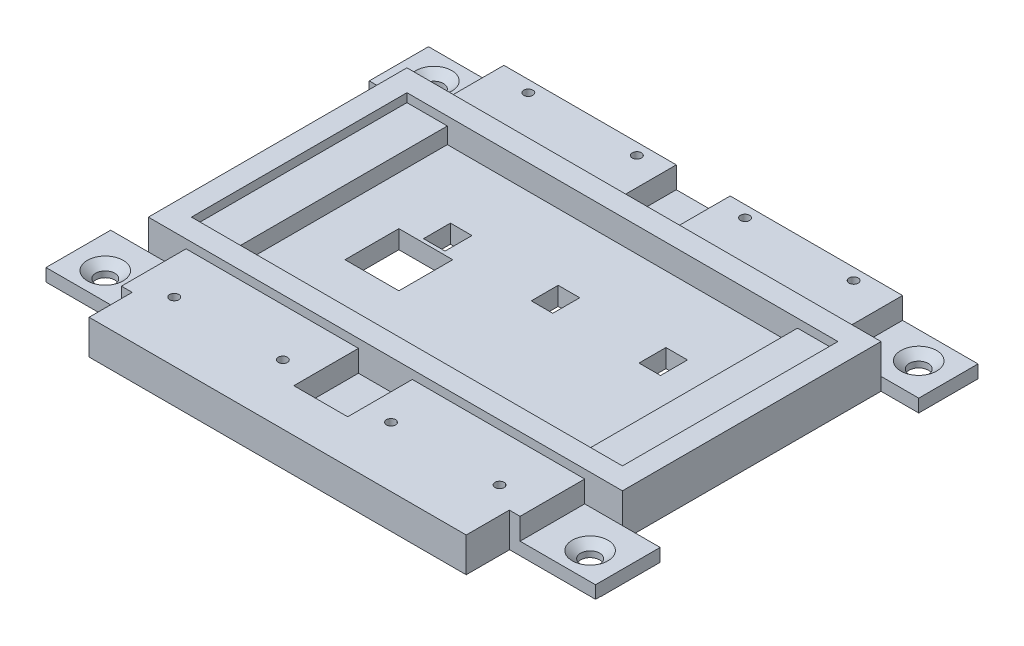
SolidWorks part; units mm, degrees
ref_plane "Front Plane" through (0, 0, 0) normal (0, 0, 1) x (1, 0, 0)
ref_plane "Top Plane" through (0, 0, 0) normal (0, 1, 0) x (1, 0, 0)
ref_plane "Right Plane" through (0, 0, 0) normal (1, 0, 0) x (0, 0, -1)
sketch "Sketch5" plane through (0, 5.08, 0) normal (0, 1, 0) x (1, 0, 0)
  line L0 (5.08, 5.08) -> (5.08, 248.92) construction
  line L1 (5.08, 105.41) -> (134.62, 105.41)
  line L2 (5.08, 105.41) -> (5.08, 16.51)
  line L3 (5.08, 16.51) -> (134.62, 16.51)
  line L4 (134.62, 105.41) -> (134.62, 16.51)
  line L6 (134.62, 248.92) -> (134.62, 5.08) construction
  point P8 (134.62, 60.96)
  dimension "D1" = 60.96
  dimension "D2" = 88.9
extrude "Button Support" add sketch "Sketch5" along normal blind 48.768
ref_plane "Plane1" through (0, 0, -60.96) normal (0, 0, 1) x (1, 0, 0)
sketch "Sketch6" plane through (0, 53.848, 0) normal (0, 1, 0) x (1, 0, 0)
  line L0 (0, 0) -> (139.7, 0) construction
  line L1 (19.05, 86.36) -> (120.65, 86.36)
  line L2 (19.05, 86.36) -> (19.05, 35.56)
  line L3 (19.05, 35.56) -> (120.65, 35.56)
  line L4 (120.65, 86.36) -> (120.65, 35.56)
  line L5 (125.73, 91.44) -> (13.97, 91.44)
  line L6 (125.73, 91.44) -> (125.73, 30.48)
  line L7 (125.73, 30.48) -> (13.97, 30.48)
  line L8 (13.97, 91.44) -> (13.97, 30.48)
  line L9 (134.62, 105.41) -> (5.08, 105.41) construction
  point P8 (69.85, 91.44)
  point P9 (69.85, 86.36)
  point P10 (120.65, 60.96)
  point P11 (125.73, 60.96)
  point P16 (69.85, 105.41)
  dimension "D1" = 50.8
  dimension "D2" = 60.96
  dimension "D3" = 101.6
  dimension "D4" = 5.08
  dimension "D5" = 5.08
extrude "Boss-Extrude4" add sketch "Sketch6" along normal blind 2.032
sketch "Sketch7" plane through (0, 53.848, 0) normal (0, 1, 0) x (1, 0, 0)
  line L0 (19.05, 35.56) -> (120.65, 35.56) construction
  line L1 (28.575, 35.56) -> (111.125, 35.56)
  line L2 (28.575, 35.56) -> (28.575, 86.36)
  line L3 (28.575, 86.36) -> (111.125, 86.36)
  line L4 (111.125, 35.56) -> (111.125, 86.36)
  line L5 (120.65, 86.36) -> (19.05, 86.36) construction
  point P8 (69.85, 86.36)
  point P9 (69.85, 35.56)
  dimension "D1" = 82.55
  dimension "D2" = 50.8
extrude "Force Sensor Cutout" cut sketch "Sketch7" against normal blind 3.81
sketch "Sketch4" plane through (0, 0, 0) normal (0, 0, 1) x (1, 0, 0)
  line L0 (0, 0) -> (139.7, 0) construction
  line L1 (5.08, 45.72) -> (134.62, 45.72)
  line L2 (5.08, 45.72) -> (5.08, 5.08)
  line L3 (5.08, 5.08) -> (134.62, 5.08)
  line L4 (134.62, 45.72) -> (134.62, 5.08)
  line L5 (0, 5.08) -> (0, 0) construction
  line L6 (139.7, 5.08) -> (139.7, 0) construction
  line L7 (0, 55.88) -> (139.7, 55.88) construction
  dimension "D1" = 5.08
  dimension "D2" = 5.08
  dimension "D3" = 5.08
  dimension "D4" = 10.16
extrude "Bottom Cut" cut sketch "Sketch4" against normal blind 139.7
sketch "Sketch8" plane through (0, 50.038, 0) normal (0, 1, 0) x (1, 0, 0)
  line L0 (120.65, 86.36) -> (19.05, 86.36) construction
  line L1 (70.358, 64.353) -> (75.438, 64.353)
  line L2 (70.358, 64.353) -> (70.358, 70.703)
  line L3 (70.358, 70.703) -> (75.438, 70.703)
  line L4 (75.438, 64.353) -> (75.438, 70.703)
  line L5 (120.65, 35.56) -> (120.65, 86.36) construction
  line L6 (95.758, 64.353) -> (95.758, 70.703)
  line L7 (95.758, 64.353) -> (100.838, 64.353)
  line L8 (100.838, 64.353) -> (100.838, 70.703)
  line L9 (95.758, 70.703) -> (100.838, 70.703)
  line L10 (44.958, 64.353) -> (44.958, 70.703)
  line L11 (44.958, 64.353) -> (50.038, 64.353)
  line L12 (50.038, 64.353) -> (50.038, 70.703)
  line L13 (44.958, 70.703) -> (50.038, 70.703)
  dimension "D1" = 15.657
  dimension "D2" = 45.212
  dimension "D3" = 5.08
  dimension "D4" = 6.35
  dimension "D5" = 2
  dimension "D6" = 2
extrude "Haptic Wire Holes" cut sketch "Sketch8" against normal up to surface (4.318 mm away) up to face at (69.85, 45.72, -60.96)
sketch "Sketch9" plane through (0, 50.038, 0) normal (0, 1, 0) x (1, 0, 0)
  line L0 (120.65, 86.36) -> (19.05, 86.36) construction
  line L1 (52.705, 63.5) -> (40.005, 63.5)
  line L2 (52.705, 63.5) -> (52.705, 50.8)
  line L3 (52.705, 50.8) -> (40.005, 50.8)
  line L4 (40.005, 63.5) -> (40.005, 50.8)
  line L5 (28.575, 86.36) -> (28.575, 35.56) construction
  dimension "D1" = 12.7
  dimension "D2" = 12.7
  dimension "D3" = 22.86
  dimension "D4" = 11.43
extrude "Force Sensor Hole" cut sketch "Sketch9" against normal up to surface (4.318 mm away) up to face at (47.498, 45.72, -67.528)
sketch "Sketch10" plane through (0, 53.848, 0) normal (0, 1, 0) x (1, 0, 0)
  line L0 (5.08, 16.51) -> (134.62, 16.51) construction
  line L1 (134.62, 105.41) -> (134.62, 16.51) construction
  line L2 (-4.4704, 60.96) -> (4.4704, 60.96) construction
  circle A0 centre (108.0186, 19.2295) radius 1.0795
  circle A4 centre (82.4261, 19.2295) radius 1.0795
  circle A5 centre (56.9186, 19.2295) radius 1.0795
  circle A6 centre (31.3261, 19.2295) radius 1.0795
  circle A7 centre (31.3261, 102.6905) radius 1.0795
  circle A8 centre (56.9186, 102.6905) radius 1.0795
  circle A9 centre (82.4261, 102.6905) radius 1.0795
  circle A10 centre (108.0186, 102.6905) radius 1.0795
  dimension "D1" = 2.159
  dimension "D2" = 2.7195
  dimension "D3" = 26.6014
  dimension "D5" = 25.5925
  dimension "D6" = 25.5075
  dimension "D4" = 25.5925
extrude "NeoPixel Holes" cut sketch "Sketch10" against normal up to surface (8.128 mm away) up to face at (46.355, 45.72, -57.15)
sketch "Sketch18" plane through (0, 53.848, 0) normal (0, 1, 0) x (1, 0, 0)
  line L0 (134.62, 248.92) -> (134.62, 5.08) construction
  line L1 (125.73, 91.44) -> (134.62, 91.44)
  line L2 (125.73, 91.44) -> (125.73, 30.48)
  line L3 (125.73, 30.48) -> (134.62, 30.48)
  line L4 (134.62, 91.44) -> (134.62, 30.48)
  line L5 (5.08, 105.41) -> (5.08, 16.51) construction
  line L6 (13.97, 91.44) -> (5.08, 91.44)
  line L7 (13.97, 91.44) -> (13.97, 30.48)
  line L8 (13.97, 30.48) -> (5.08, 30.48)
  line L9 (5.08, 91.44) -> (5.08, 30.48)
  line L10 (13.97, 30.48) -> (125.73, 30.48) construction
extrude "Neopixel Wire Side Holes" cut sketch "Sketch18" against normal up to next
sketch "Sketch19" plane through (0, 53.848, 0) normal (0, 1, 0) x (1, 0, 0)
  line L0 (25.4, 105.41) -> (5.08, 105.41) construction
  line L1 (76.2, 105.41) -> (63.5, 105.41)
  line L2 (76.2, 105.41) -> (76.2, 91.44)
  line L3 (76.2, 91.44) -> (63.5, 91.44)
  line L4 (63.5, 105.41) -> (63.5, 91.44)
  line L5 (22.86, 105.41) -> (5.08, 105.41)
  line L6 (22.86, 105.41) -> (22.86, 91.44)
  line L7 (22.86, 91.44) -> (5.08, 91.44)
  line L8 (5.08, 105.41) -> (5.08, 91.44)
  line L9 (5.08, 105.41) -> (5.08, 91.44) construction
  line L10 (134.62, 105.41) -> (5.08, 105.41) construction
  line L11 (134.62, 105.41) -> (116.84, 105.41)
  line L12 (134.62, 105.41) -> (134.62, 91.44)
  line L13 (134.62, 91.44) -> (116.84, 91.44)
  line L14 (116.84, 105.41) -> (116.84, 91.44)
  line L15 (125.73, 91.44) -> (13.97, 91.44) construction
  point P19 (69.85, 105.41)
  point P20 (69.85, 105.41)
  dimension "D1" = 12.7
  dimension "D2" = 17.78
extrude "NeoPixel solder gap" cut sketch "Sketch19" against normal blind 5.08
mirror "Mirror1" about plane through (0, 0, -60.96) normal (0, 0, 1) of "NeoPixel solder gap"
sketch "Sketch20" plane through (0, 0, -16.51) normal (0, 0, 1) x (1, 0, 0)
  line L0 (134.62, 48.768) -> (134.62, 45.72) construction
  line L1 (5.08, 48.768) -> (134.62, 48.768)
  line L2 (5.08, 48.768) -> (5.08, 45.7868)
  line L3 (5.08, 45.7868) -> (134.62, 45.7868)
  line L4 (134.62, 48.768) -> (134.62, 45.7868)
  line L6 (116.84, 53.848) -> (76.2, 53.848)
  line L7 (116.84, 53.848) -> (116.84, 48.768)
  line L8 (116.84, 48.768) -> (76.2, 48.768)
  line L9 (76.2, 53.848) -> (76.2, 48.768)
  line L10 (22.86, 53.848) -> (63.5, 53.848)
  line L11 (22.86, 53.848) -> (22.86, 48.768)
  line L12 (22.86, 48.768) -> (63.5, 48.768)
  line L13 (63.5, 53.848) -> (63.5, 48.768)
  line M5 (116.84, 48.768) -> (116.84, 53.848)
  line M6 (116.84, 53.848) -> (76.2, 53.848)
  line M7 (76.2, 53.848) -> (76.2, 48.768)
  line M8 (76.2, 48.768) -> (63.5, 48.768)
  line M9 (63.5, 48.768) -> (63.5, 53.848)
  line M10 (63.5, 53.848) -> (22.86, 53.848)
  line M11 (22.86, 53.848) -> (22.86, 48.768)
  line M12 (22.86, 48.768) -> (5.08, 48.768)
  line M13 (5.08, 48.768) -> (5.08, 45.72)
  line M15 (134.62, 45.72) -> (134.62, 48.768)
  line M16 (134.62, 48.768) -> (116.84, 48.768)
extrude "Boss-Extrude6" add sketch "Sketch20" along normal blind 1.27 contours L1 M7 M5 M6 | L3 L1 M13 M15 M16 M8 M12 | L1 M11 M9 M10 region at (69.85, 47.2774, -16.51) region at (43.18, 51.308, -16.51) region at (96.52, 51.308, -16.51)
sketch "Sketch11" plane through (0, 0, -15.24) normal (0, 0, 1) x (1, 0, 0)
  line L0 (5.08, 45.7868) -> (5.08, 45.72) construction
  line L1 (25.4, 53.848) -> (114.3, 53.848)
  line L2 (25.4, 53.848) -> (25.4, 45.72)
  line L3 (25.4, 45.72) -> (114.3, 45.72)
  line L4 (114.3, 53.848) -> (114.3, 45.72)
  line L5 (134.62, 45.7868) -> (134.62, 45.72) construction
  line L6 (5.08, 53.848) -> (134.62, 53.848) construction
  line L7 (5.08, 45.72) -> (134.62, 45.72) construction
  dimension "D1" = 20.32
  dimension "D2" = 20.32
extrude "Boss-Extrude5" add sketch "Sketch11" along normal blind 10.16
hole_wizard "CSK for #8 Flat Head Machine Screw (100)1" positions "Sketch21" profile "Sketch22" countersink size "#8" standard "ANSI Inch" end condition through all
sketch "Sketch21" plane through (0, 48.768, 0) normal (0, 1, 0) x (1, 0, 0)
  line L0 (134.62, 91.44) -> (134.62, 105.41) construction
  line L1 (134.62, 105.41) -> (116.84, 105.41) construction
  line L2 (22.86, 15.24) -> (5.08, 15.24) construction
  line L3 (5.08, 15.24) -> (5.08, 30.48) construction
  point P0 (12.7, 99.06)
  point P2 (127, 99.06)
  point P4 (127, 21.59)
  point P6 (12.7, 21.59)
  dimension "D1" = 7.62
  dimension "D2" = 6.35
  dimension "D3" = 6.35
  dimension "D4" = 7.62
sketch "Sketch22" plane through (12.7, 48.768, -99.06) normal (1, 0, 0) x (0, 0, 1)
  line L0 (0, 0) -> (0, 3.048)
  line L1 (0, 3.048) -> (2.2479, 3.048)
  line L2 (2.2479, 3.048) -> (2.2479, 1.6518)
  line L3 (2.2479, 1.6518) -> (4.2164, 0)
  line L5 (4.2164, 0) -> (0, 0)
  line L6 (-2.2479, 1.6518) -> (-4.2164, 0) construction
  line L11 (0, -6.35) -> (0, 107.95) construction
  dimension "Thru Hole Dia." = 4.4958
  dimension "Thru Hole Depth" = 3.048
  dimension "Near C'Sink Dia." = 8.4328
  dimension "Near C'Sink Angle" = 100
equation "\"Arrow Height\"= 1.5in"
equation "\"Button Height\"= 2in"
equation "\"Button Width\"= 4in"
equation "\"Haptic Diameter\"= 10mm"
equation "\"Haptic Thickness\"= 2.7mm"
equation "\"Arrow Spacing\"= 1in"
equation "\"Arrow Width\"= 1in"
equation "\"Haptic Wire Angle\"= 63.43"
equation "\"Haptic Wire Width\" = .2in"
equation "\"Haptic Wire Height\" = .25in"
equation "\"Mounting Bolt Hole Diameter\"= .14in"
equation "\"D3@Sketch8\"=\"Haptic Wire Width\""
equation "\"D4@Sketch8\"=\"Haptic Wire Height\""
